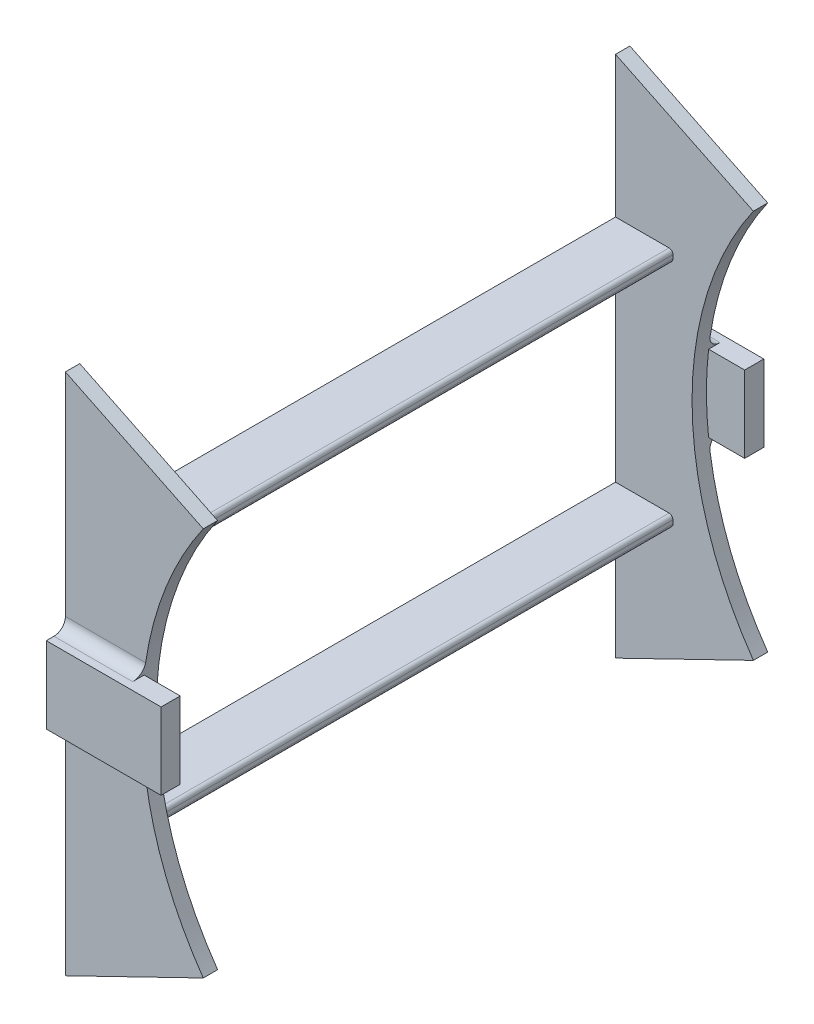
SolidWorks part; units mm, degrees
material "ABS"
ref_plane "Front Plane" through (0, 0, 0) normal (0, 0, 1) x (1, 0, 0)
ref_plane "Top Plane" through (0, 0, 0) normal (0, 1, 0) x (1, 0, 0)
ref_plane "Right Plane" through (0, 0, 0) normal (1, 0, 0) x (0, 0, -1)
sketch "Sketch1" plane through (0, 0, 0) normal (0, 0, 1) x (1, 0, 0)
  line L0 (0, 0) -> (-88.611, 0) construction
  line L1 (-88.611, 0) -> (-108.611, 0) construction
  line L2 (-72.5859, -50.8252) -> (-108.611, -50.8252) construction
  line L3 (-108.611, -50.8252) -> (-108.611, -68.3252) construction
  line L4 (-72.5859, -50.8252) -> (-108.611, -68.3252)
  line L5 (-108.611, -68.3252) -> (-108.611, 68.3252)
  line L6 (-108.611, 50.8252) -> (-108.611, 68.3252) construction
  line L7 (-72.5859, 50.8252) -> (-108.611, 50.8252) construction
  line L8 (-72.5859, 50.8252) -> (-108.611, 68.3252)
  line L9 (0, 0) -> (-83.2671, 30.3067) construction
  line L10 (0, 0) -> (-83.2671, -30.3067) construction
  circle A0 centre (0, 0) radius 88.611 construction
  arc A1 (-72.5859, 50.8252) -> (-72.5859, -50.8252) centre (0, 0) ccw
  point P14 (-88.611, 0)
  dimension "D1" = 177.222
  dimension "D2" = 20
  dimension "D3" = 17.5
  dimension "D4" = 20
extrude "Boss-Extrude1" add sketch "Sketch1" along normal mid plane 3.75
ref_plane "Plane1" through (-83.2671, 0, 0) normal (1, 0, 0) x (0, 0, -1)
sketch "Sketch2" plane through (-83.2671, 0, 0) normal (1, 0, 0) x (0, 0, -1)
  circle A0 centre (0, 30.3067) radius 0.75
  dimension "D1" = 1.5
sketch "Sketch3" plane through (0, 0, 1.875) normal (0, 0, 1) x (1, 0, 0)
  line L0 (0, 0) -> (-108.611, 0) construction
  line L1 (-108.611, 68.3252) -> (-108.611, -68.3252) construction
  line L2 (-108.611, 0) -> (-93.611, 0) construction
  line L3 (-93.611, 0) -> (-93.611, -30) construction
  line L4 (-93.611, -30) -> (-108.611, -30) construction
  line L5 (-108.611, -68.3252) -> (-108.611, 68.3252) construction
  line L6 (-108.611, -31.5) -> (-94.611, -31.5)
  line L7 (-108.611, -31.5) -> (-108.611, -28.5)
  line L8 (-108.611, -28.5) -> (-94.611, -28.5)
  line L9 (-93.611, -30.5) -> (-93.611, -29.5)
  line L10 (-108.611, -31.5) -> (-93.611, -28.5) construction
  line L11 (-108.611, -28.5) -> (-93.611, -31.5) construction
  arc A0 (-94.611, -28.5) -> (-93.611, -29.5) centre (-94.611, -29.5) cw
  arc A1 (-94.611, -31.5) -> (-93.611, -30.5) centre (-94.611, -30.5) ccw
  point P5 (-101.111, -30)
  dimension "D3" = 3
  dimension "D4" = 1
  dimension "D1" = 15
  dimension "D2" = 30
extrude "Boss-Extrude3" add sketch "Sketch3" along normal blind 140 contours L7 L6 A1 L9 A0 L8
mirror "Mirror2" about plane through (0, 0, 0) normal (0, 1, 0) of "Boss-Extrude3"
sketch "Sketch6" plane through (-83.2671, 0, 0) normal (1, 0, 0) x (0, 0, -1)
  line L0 (0, 0) -> (-1.875, 0)
  line L1 (-1.875, 0) -> (-71.875, 0)
  line L2 (-71.875, 0) -> (-71.875, -50000) construction
  dimension "D1" = 1.875
  dimension "D2" = 70
ref_plane "Plane2" through (0, 0, 71.875) normal (0, 0, 1) x (0, -1, 0)
mirror "Mirror7" about plane through (0, 0, 71.875) normal (0, 0, 1) of "Boss-Extrude1"
sketch "Sketch4" plane through (0, 0, -1.875) normal (0, 0, -1) x (-1, 0, 0)
  line L0 (0, 0) -> (108.611, 0) construction
  line L1 (108.611, 68.3252) -> (108.611, -68.3252) construction
  line L2 (108.611, 0) -> (108.611, 10)
  line L3 (108.611, 0) -> (108.611, -10)
  line L4 (108.611, -10) -> (78.611, -10)
  line L5 (78.611, -10) -> (78.611, 10)
  line L6 (78.611, 10) -> (108.611, 10)
  dimension "D1" = 10
  dimension "D2" = 10
  dimension "D3" = 30
extrude "Boss-Extrude4" add sketch "Sketch4" along normal blind 5
mirror "Mirror10" about plane through (0, 0, 71.875) normal (0, 0, 1) of "Boss-Extrude4"
fillet "Fillet4" radius 3 4 edges at (-98.328, -10, -1.875) (-98.328, 10, -1.875) (-98.328, 10, 145.625) (-98.328, -10, 145.625)
equation "\"OuterThickness\"= 3mm"
equation "\"MasterFillet\"= 3mm"
equation "\"PartSeperation\"= 6mm"
equation "\"Tolerance\"= 0.15mm"
equation "\"HeightPart\"= 100mm"
equation "\"Holes\"= 1.5mm"
equation "\"SpineHolderThickness\"= 3mm"
equation "\"SpineHolderDepth\" = 3mm"
equation "\"MotorLength\" = 40.5mm"
equation "\"MotorWidth\" = 20.3mm"
equation "\"AttachmentHeight\"= 3mm"
equation "\"SpoolDiameter\"= 60mm"
equation "\"SpoolHeight\"= 2mm"
equation "\"SpoolRidgeHeight\"= 1mm"
equation "\"SpoolRidgeDepth\"= 2mm"
equation "\"SpoolSeperation\"= 2mm"
equation "\"ServoHolderWidthOffset\"= 20mm"
equation "\"MotorTransmitterToScrew\"= 21.7mm"
equation "\"SpoolToSpine\"= 15mm"
equation "\"SpoolCenterToMotor\" = 31.5mm"
equation "\"HubOffset\"= 18mm"
equation "\"D1@Sketch1\"=2*(((\"SpoolToSpine\"+\"SpoolDiameter\"/2+\"SpoolRidgeDepth\" -\"SpoolCenterToMotor\" -((\"MotorLength\"+\"ServoHolderWidthOffset\")-(\"MotorLength\"+\"Tolerance\"*2))/2 +(\"MotorLength\"+\"ServoHolderWidthOffset\"))^2 + (\"MotorTransmitterToScrew\"+3)^2)^(1/2)+\"HubOffset\")"
equation "\"D1@Boss-Extrude1\"=\"SpineHolderDepth\"*1.25"
equation "\"D1@Sketch2\"=\"SpineHolderDepth\"*0.5"
equation "\"D1@Boss-Extrude3\"=(3*((\"SpoolDiameter\"/3)*2+\"SpoolRidgeDepth\"*2+\"SpoolSeperation\")+\"SpoolSeperation\")"
equation "\"D1@Sketch6\"=(\"SpineHolderThickness\"*1.25)/2"
equation "\"D2@Sketch6\"=((3*((\"SpoolDiameter\"/3)*2+\"SpoolRidgeDepth\"*2+\"SpoolSeperation\")+\"SpoolSeperation\"))/2"
equation "\"DiscThickness\"= 4mm"
equation "\"LigamentThickness\"= 2mm"
equation "\"LigamentExtension\"= 1mm"
equation "\"LigamentAngle\"= 20deg"
equation "\"SpineDiameter\"= 15mm"
equation "\"LigamentDepth\"= 1mm"
equation "\"ServoFastenerHolders\"=2mm"
equation "\"ArduinoLength\" = 53.4mm"
equation "\"ArduinoWidth\" = 50mm"
equation "\"ArdYOffset\" = 29.5mm"
equation "\"ArdXOffset\" = 20.5mm"
equation "\"ArdXOffsetSmall\" = 25mm"
equation "\"MiddleServoOffset\"= 12mm"
equation "\"LargeServoOffset\"= 3mm"
equation "\"SmallServoOffset\"= 0mm"
equation "\"ToolHoleDiameter\"= 12mm"
equation "\"D1\" = \"SpineHolderDepth\" / 4"
equation "\"OuterDiameter\"= 15mm"
